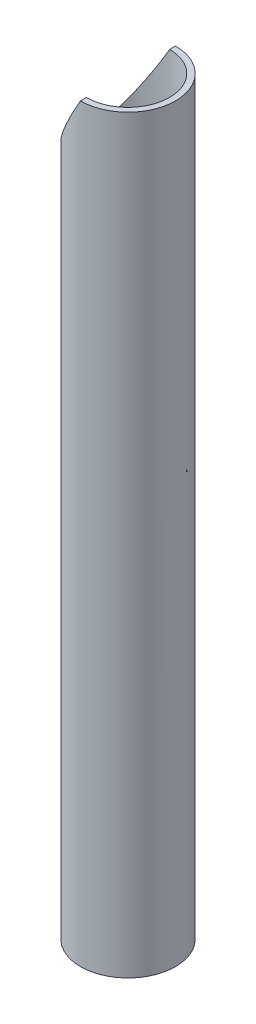
SolidWorks part; units mm, degrees
ref_plane "Front Plane" through (0, 0, 0) normal (0, 0, 1) x (1, 0, 0)
ref_plane "Top Plane" through (0, 0, 0) normal (0, 1, 0) x (1, 0, 0)
ref_plane "Right Plane" through (0, 0, 0) normal (1, 0, 0) x (0, 0, -1)
sketch "Sketch1" plane through (0, 0, 0) normal (0, 1, 0) x (1, 0, 0)
  circle A0 centre (0, 0) radius 7
  circle A1 centre (0, 0) radius 8
  dimension "D1" = 14
  dimension "D2" = 16
extrude "Boss-Extrude1" add sketch "Sketch1" along normal blind 126.216
sketch "Sketch2" plane through (0, 0, 0) normal (0, 0, 1) x (1, 0, 0)
  line L0 (0, 126.216) -> (-8, 112.3596)
  line L1 (8, 126.216) -> (-8, 126.216) construction
  line L2 (-8, 126.216) -> (-8, 0) construction
  line L3 (-8, 112.3596) -> (-8, 126.216)
  line L4 (-8, 126.216) -> (0, 126.216)
  dimension "D1" = 60
extrude "Cut-Extrude1" cut sketch "Sketch2" against normal blind 25 and the other way blind 25
equation "\"D1@Boss-Extrude1\"=150*cos(45)+20.15"
